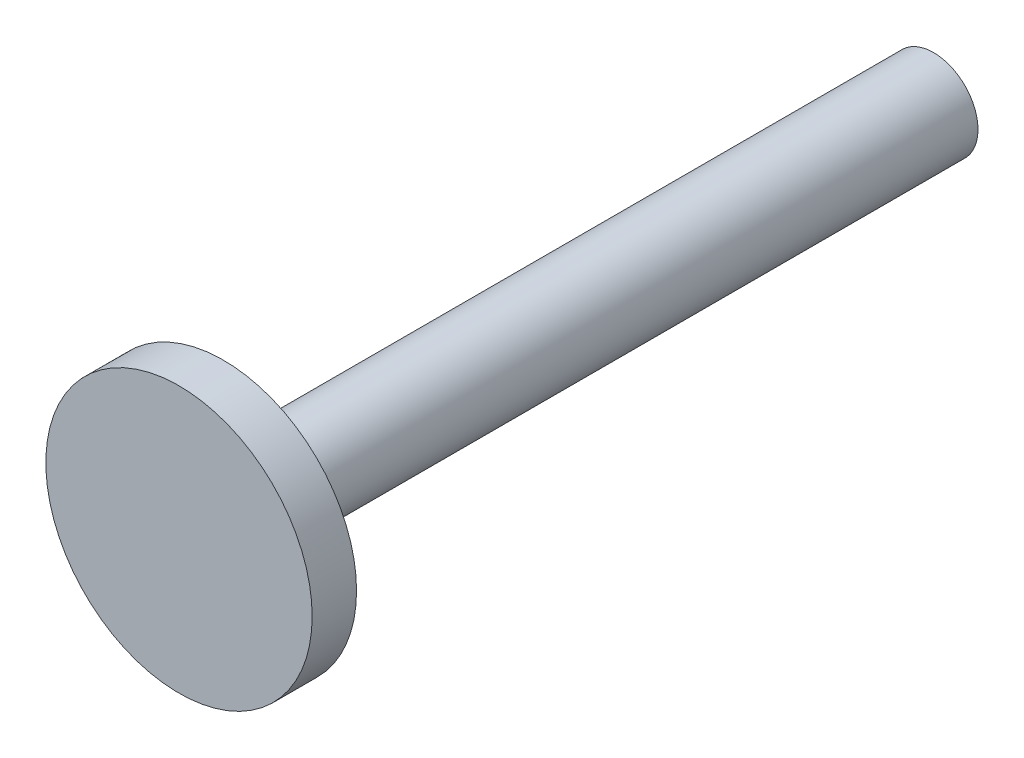
SolidWorks part; units mm, degrees
material "ABS"
ref_plane "Front Plane" through (0, 0, 0) normal (0, 0, 1) x (1, 0, 0)
ref_plane "Top Plane" through (0, 0, 0) normal (0, 1, 0) x (1, 0, 0)
ref_plane "Right Plane" through (0, 0, 0) normal (1, 0, 0) x (0, 0, -1)
sketch "Sketch1" plane through (0, 0, 0) normal (0, 0, 1) x (1, 0, 0)
  circle A0 centre (0, 0) radius 10
  circle A1 centre (0, 0) radius 10 construction
extrude "Boss-Extrude1" add sketch "Sketch1" against normal blind 150 and the other way blind 10
sketch "Sketch2" plane through (0, 0, 10) normal (0, 0, 1) x (1, 0, 0)
  circle A0 centre (0, 0) radius 30
  circle A1 centre (0, 0) radius 30 construction
extrude "Boss-Extrude2" add sketch "Sketch2" along normal blind 10
shell "Shell1" thickness 1
sketch "Sketch3" plane through (0, 0, 20) normal (0, 0, 1) x (1, 0, 0)
  circle A0 centre (0, 0) radius 30 construction
  point P0 (0, 0)
